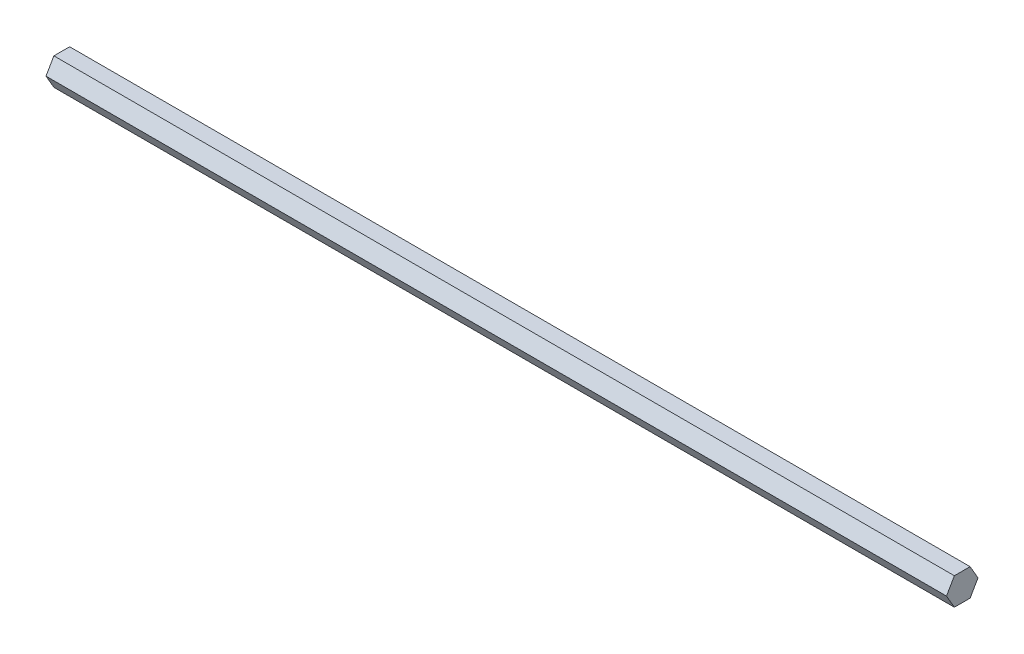
SolidWorks part; units mm, degrees
material "7075-T6 (SN)"
ref_plane "Front Plane" through (0, 0, 0) normal (0, 0, 1) x (1, 0, 0)
ref_plane "Top Plane" through (0, 0, 0) normal (0, 1, 0) x (1, 0, 0)
ref_plane "Right Plane" through (0, 0, 0) normal (1, 0, 0) x (0, 0, -1)
sketch "Sketch1" plane through (0, 0, 0) normal (1, 0, 0) x (0, 0, -1)
  line L1 (7.3323, 0) -> (3.6662, 6.35)
  line L2 (3.6662, 6.35) -> (-3.6662, 6.35)
  line L3 (-3.6662, 6.35) -> (-7.3323, 0)
  line L4 (-7.3323, 0) -> (-3.6662, -6.35)
  line L5 (-3.6662, -6.35) -> (3.6662, -6.35)
  line L6 (3.6662, -6.35) -> (7.3323, 0)
  circle A0 centre (0, 0) radius 6.35 construction
  dimension "D1" = 12.7
extrude "Boss-Extrude1" add sketch "Sketch1" along normal mid plane 419.1
ref_axis "Axis1" through (-230.505, 0, 0) along (1, 0, 0)
